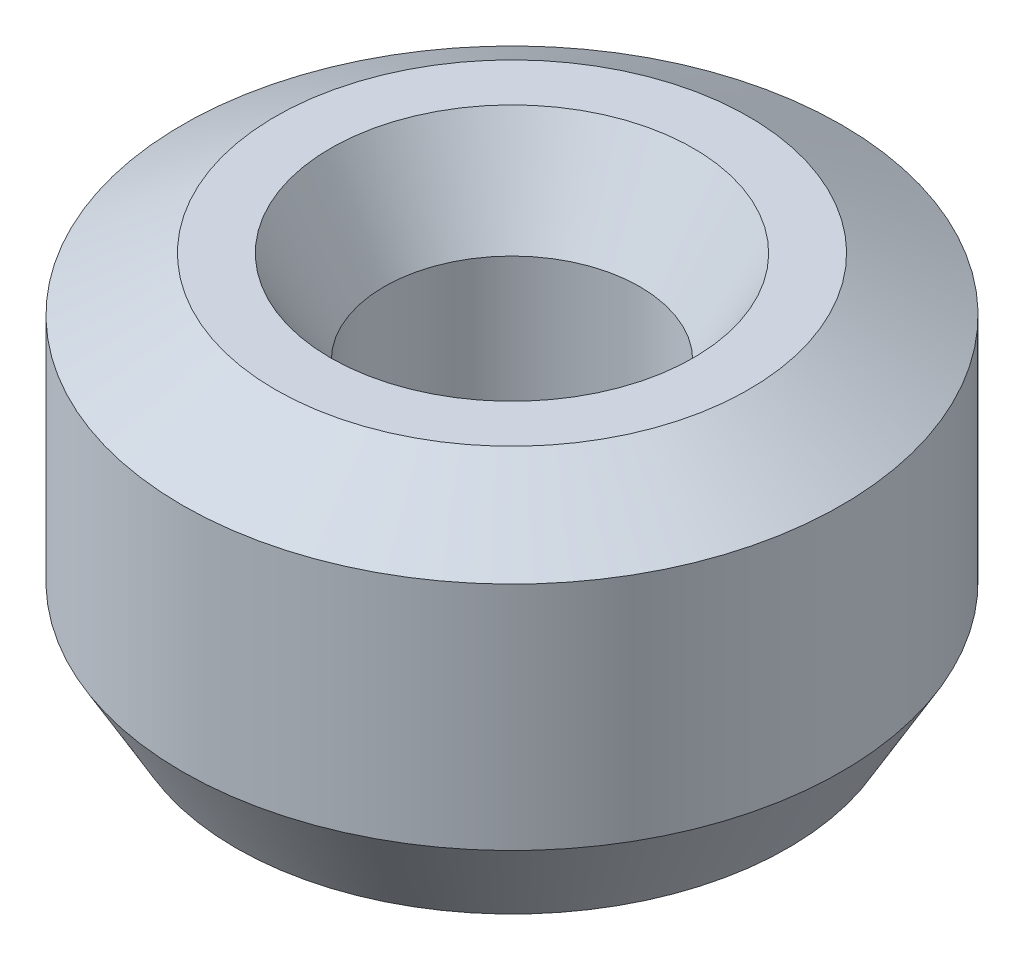
SolidWorks part; units mm, degrees
ref_plane "Front Plane" through (0, 0, 0) normal (0, 0, 1) x (1, 0, 0)
ref_plane "Top Plane" through (0, 0, 0) normal (0, 1, 0) x (1, 0, 0)
ref_plane "Right Plane" through (0, 0, 0) normal (1, 0, 0) x (0, 0, -1)
sketch "Sketch1" plane through (0, 0, 0) normal (0, 1, 0) x (1, 0, 0)
  circle A0 centre (0, 0) radius 22.5
  dimension "SLEEVE_OD" = 45
extrude "Boss-Extrude1" add sketch "Sketch1" along normal blind 25.7635
sketch "Sketch2" plane through (0, 0, 0) normal (0, 1, 0) x (1, 0, 0)
  circle A0 centre (0, 0) radius 8.7282
  dimension "BORE_D" = 17.4565
extrude "Cut-Extrude1" cut sketch "Sketch2" along normal through all
chamfer "Chamfer1" distance 3.664 angle 60 4 edges at (0, 25.7635, 8.7282) (0, 0, 8.7282) (0, 0, 22.5) (0, 25.7635, 22.5) first distance on face at (0, 25.7635, 8.7282) first distance on face at (0, 0, 8.7282) first distance on face at (0, 25.7635, 22.5)
